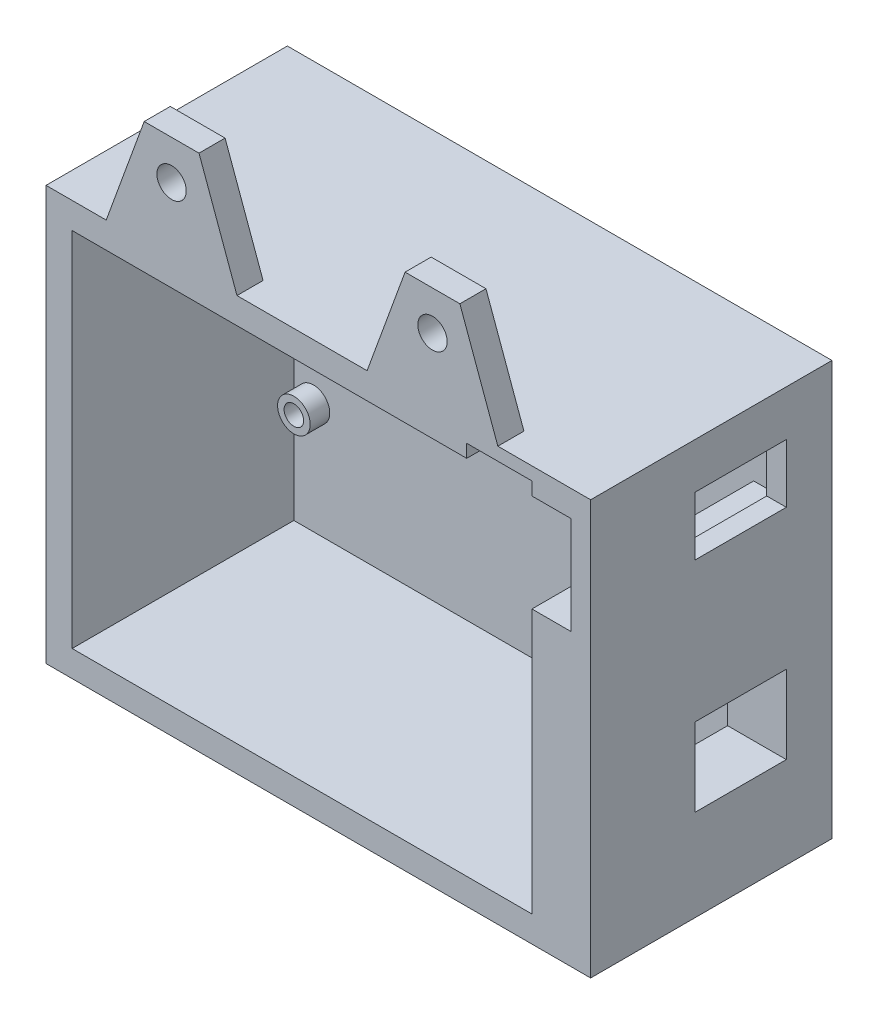
SolidWorks part; units mm, degrees
ref_plane "前视基准面" through (0, 0, 0) normal (0, 0, 1) x (1, 0, 0)
ref_plane "上视基准面" through (0, 0, 0) normal (0, 1, 0) x (1, 0, 0)
ref_plane "右视基准面" through (0, 0, 0) normal (1, 0, 0) x (0, 0, -1)
sketch "草图1" plane through (0, 0, 0) normal (0, 0, 1) x (1, 0, 0)
  line L0 (41.25, -5.75) -> (44.25, -5.75) construction
  line L1 (-35.25, -27.75) -> (35.25, -27.75)
  line L2 (-35.25, -27.75) -> (-35.25, 27.75)
  line L3 (-35.25, 27.75) -> (35.25, 27.75)
  line L4 (35.25, -27.75) -> (35.25, 27.75)
  line L5 (-35.25, -27.75) -> (35.25, 27.75) construction
  line L6 (-35.25, 27.75) -> (35.25, -27.75) construction
  line L7 (44.25, -5.75) -> (44.25, -17.75) construction
  line L8 (44.25, -17.75) -> (41.25, -17.75) construction
  line L9 (41.25, -17.75) -> (41.25, -27.75)
  line L10 (41.25, -27.75) -> (35.25, -27.75)
  line L11 (35.25, 27.75) -> (41.25, 27.75)
  line L12 (41.25, 27.75) -> (41.25, -5.75)
  line L13 (0, 0) -> (35.25, 0) construction
  line L14 (44.25, -31.75) -> (44.25, 31.75)
  line L15 (44.25, 31.75) -> (-39.25, 31.75)
  line L16 (-39.25, 31.75) -> (-39.25, -31.75)
  line L17 (-39.25, -31.75) -> (44.25, -31.75)
  line L18 (44.25, -5.75) -> (41.25, -5.75)
  line L19 (41.25, -17.75) -> (44.25, -17.75)
  line L20 (41.25, -5.75) -> (35.25, -5.75)
  line L21 (41.25, -17.75) -> (35.25, -17.75)
  line L22 (35.25, 12.75) -> (41.25, 12.75)
  line L23 (41.25, 24.75) -> (44.25, 24.75)
  line L25 (41.25, 15.75) -> (44.25, 15.75)
  circle A0 centre (21.25, -24.75) radius 1.5
  circle A1 centre (21.25, 24.75) radius 1.5
  circle A2 centre (-32.25, -10.75) radius 1.5
  point P0 (0, 0)
  dimension "D8" = 3
  dimension "D16" = 3
  dimension "D1" = 55.5
  dimension "D2" = 70.5
  dimension "D3" = 22
  dimension "D4" = 12
  dimension "D5" = 6
  dimension "D6" = 9
  dimension "D7" = 14
  dimension "D9" = 3
  dimension "D10" = 4
  dimension "D11" = 4
  dimension "D12" = 4
  dimension "D13" = 15
  dimension "D14" = 9
  dimension "D15" = 3
  dimension "D17" = 3
  dimension "D18" = 17
extrude "凸台-拉伸1" add sketch "草图1" along normal blind 3 contours L19 L9 L10 L1 L2 L3 L11 L12 L18 L14 L15 L16 L17 | L1 L4 L3 L2 A0 A1 | L22 L4 L20 L12 | L4 L22 L12 L11 | L21 L19 L14 L18 L20 L4 | L9 L21 L4 L10 | L25 L12 L18 L14 | L12 L25 L14 L23 region at (-0.0186, 0.0195, 0) region at (0, -28.799, 0) region at (38.25, -22.75, 0) region at (39.75, -11.75, 0) region at (38.25, 20.25, 0) region at (38.25, 3.5, 0) region at (42.75, 5, 0) region at (42.75, 20.25, 0)
extrude "凸台-拉伸2" add sketch "草图1<3>" along normal blind 15 from offset 3 contours L19 L9 L10 L1 L2 L3 L11 L12 L18 L14 L15 L16 L17 | L22 L4 L20 L12 | L9 L21 L4 L10 | L25 L12 L18 L14 region at (0, -28.799, 0) region at (38.25, -22.75, 0) region at (38.25, 3.5, 0) region at (42.75, 5, 0)
sketch "草图1<3>" plane through (0, 0, 0) normal (0, 0, 1) x (1, 0, 0) same geometry as "草图1"
extrude "凸台-拉伸3" add sketch "草图1<4>" along normal blind 19 from offset 18 contours L19 L9 L10 L1 L2 L3 L11 L12 L18 L14 L15 L16 L17 | L22 L4 L20 L12 | L9 L21 L4 L10 | L25 L12 L18 L14 region at (0, -28.799, 0) region at (38.25, -22.75, 0) region at (38.25, 3.5, 0) region at (42.75, 5, 0)
sketch "草图1<4>" plane through (0, 0, 0) normal (0, 0, 1) x (1, 0, 0) same geometry as "草图1"
extrude "凸台-拉伸6" add sketch "草图1<5>" along normal blind 4 from offset 3 contours L12 L25 L14 L23 | L21 L19 L14 L18 L20 L4 region at (39.75, -11.75, 0) region at (42.75, 20.25, 0)
sketch "草图1<5>" plane through (0, 0, 0) normal (0, 0, 1) x (1, 0, 0) same geometry as "草图1"
sketch "草图6" plane through (0, 0, 37) normal (0, 0, 1) x (1, 0, 0)
  line L0 (44.25, 31.75) -> (-39.25, 31.75) construction
  line L1 (30.0248, 31.75) -> (24.2012, 47.75)
  line L2 (24.2012, 47.75) -> (15.7988, 47.75)
  line L3 (15.7988, 47.75) -> (9.9752, 31.75)
  line L4 (20, -958.25) -> (20, 49041.75) construction
  line L5 (0, -1000) -> (0, 49000) construction
  line L6 (30.0248, 31.75) -> (9.9752, 31.75)
  line L7 (-24.2012, 47.75) -> (-15.7988, 47.75)
  line L8 (-30.0248, 31.75) -> (-24.2012, 47.75)
  line L9 (-30.0248, 31.75) -> (-9.9752, 31.75)
  line L10 (-15.7988, 47.75) -> (-9.9752, 31.75)
  circle A0 centre (20, 41.75) radius 2.25
  circle A1 centre (-20, 41.75) radius 2.25
  dimension "D1" = 4.5
  dimension "D2" = 4.5
  dimension "D3" = 10
  dimension "D4" = 40
  dimension "D5" = 20
  dimension "D6" = 24.25
  dimension "D7" = 6
  dimension "D8" = 6
  dimension "D9" = 110
extrude "凸台-拉伸7" add sketch "草图6" against normal blind 4
sketch "草图7" plane through (0, 0, 37) normal (0, 0, 1) x (1, 0, 0)
  line L0 (44.25, -5.75) -> (35.25, -5.75) construction
  line L1 (41.25, 24.75) -> (44.25, 24.75)
  line L2 (41.25, 24.75) -> (41.25, 15.75)
  line L3 (41.25, 15.75) -> (44.25, 15.75)
  line L4 (44.25, 24.75) -> (44.25, 15.75)
  line L5 (44.25, -17.75) -> (35.25, -17.75)
  line L6 (44.25, -17.75) -> (44.25, -5.75)
  line L7 (44.25, -5.75) -> (35.25, -5.75)
  line L8 (35.25, -17.75) -> (35.25, -5.75)
extrude "凸台-拉伸8" add sketch "草图7" against normal offset from surface (16 mm away) 14 up to face at (42.75, 20.25, 7)
sketch "草图8" plane through (0, 0, 37) normal (0, 0, 1) x (1, 0, 0)
  line L0 (-35.25, 27.75) -> (41.25, 27.75) construction
  line L1 (35.25, 27.75) -> (25.25, 27.75)
  line L2 (35.25, 27.75) -> (35.25, 29.75)
  line L3 (35.25, 29.75) -> (25.25, 29.75)
  line L4 (25.25, 27.75) -> (25.25, 29.75)
  line L5 (35.25, -27.75) -> (35.25, 12.75) construction
  dimension "D1" = 2
  dimension "D2" = 10
extrude "切除-拉伸1" cut sketch "草图8" against normal up to surface (34 mm away) up to face at (13.75, 4.25, 3)
sketch "草图9" plane through (0, 0, 3) normal (0, 0, 1) x (1, 0, 0)
  circle A0 centre (-32.25, -10.75) radius 2.5
  circle A1 centre (21.25, 24.75) radius 2.5
  circle A2 centre (21.25, -24.75) radius 2.5
  circle A3 centre (21.25, 24.75) radius 1.5 construction
  circle A4 centre (21.25, 24.75) radius 1.5
  circle A5 centre (-32.25, -10.75) radius 1.5 construction
  circle A6 centre (21.25, -24.75) radius 1.5 construction
  circle A7 centre (-32.25, -10.75) radius 1.5
  circle A8 centre (21.25, -24.75) radius 1.5
  dimension "D1" = 5
  dimension "D2" = 5
  dimension "D3" = 5
extrude "凸台-拉伸17" add sketch "草图9" along normal blind 3
